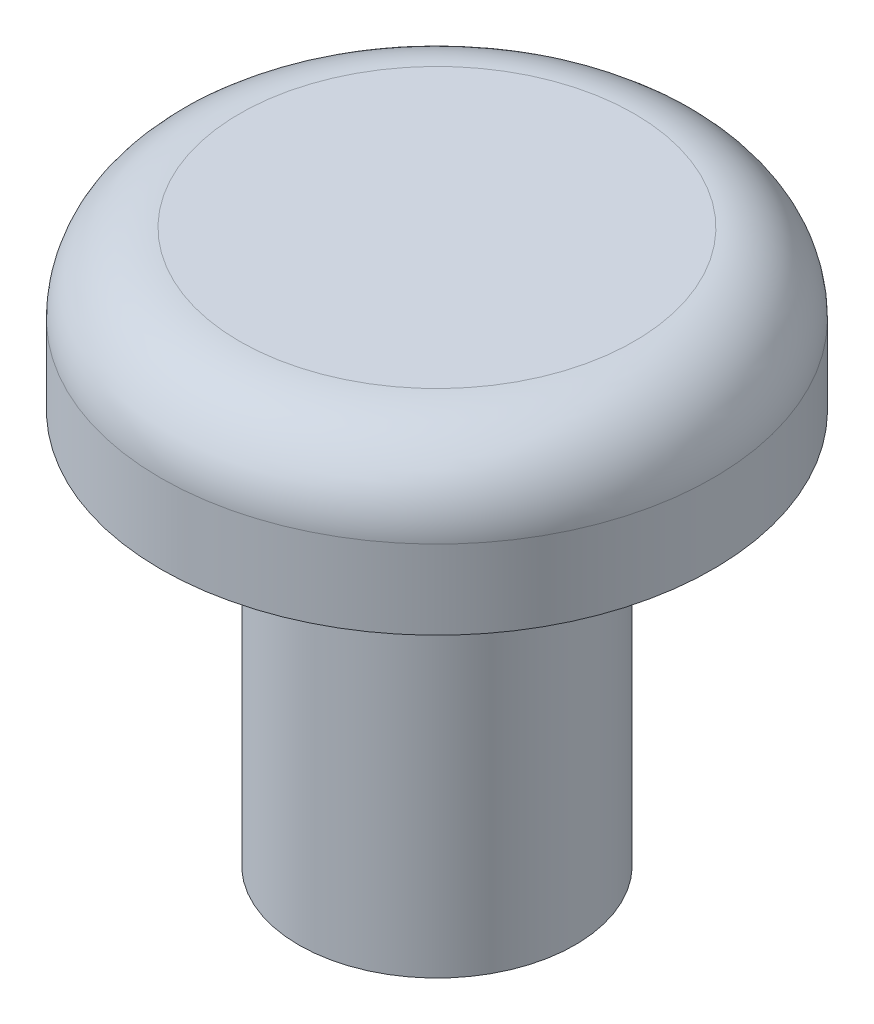
SolidWorks part; units mm, degrees
ref_plane "Face" through (0, 0, 0) normal (0, 0, 1) x (1, 0, 0)
ref_plane "Dessus" through (0, 0, 0) normal (0, 1, 0) x (1, 0, 0)
ref_plane "Droite" through (0, 0, 0) normal (1, 0, 0) x (0, 0, -1)
ref_axis "Axe2" through (0, -55, 0) along (0, 1, 0)
sketch "Esquisse1" plane through (0, 0, 0) normal (0, 1, 0) x (1, 0, 0)
  circle A0 centre (0, 0) radius 1.75
  dimension "D1" = 3.5
extrude "Boss.-Extru.1" add sketch "Esquisse1" along normal blind 5 contours A0
sketch "Esquisse2" plane through (0, 5, 0) normal (0, 1, 0) x (1, 0, 0)
  circle A0 centre (0, 0) radius 3.5
  dimension "D1" = 7
extrude "Boss.-Extru.2" add sketch "Esquisse2" along normal blind 2
fillet "Congé1" radius 1 1 edges at (0, 7, 3.5)
